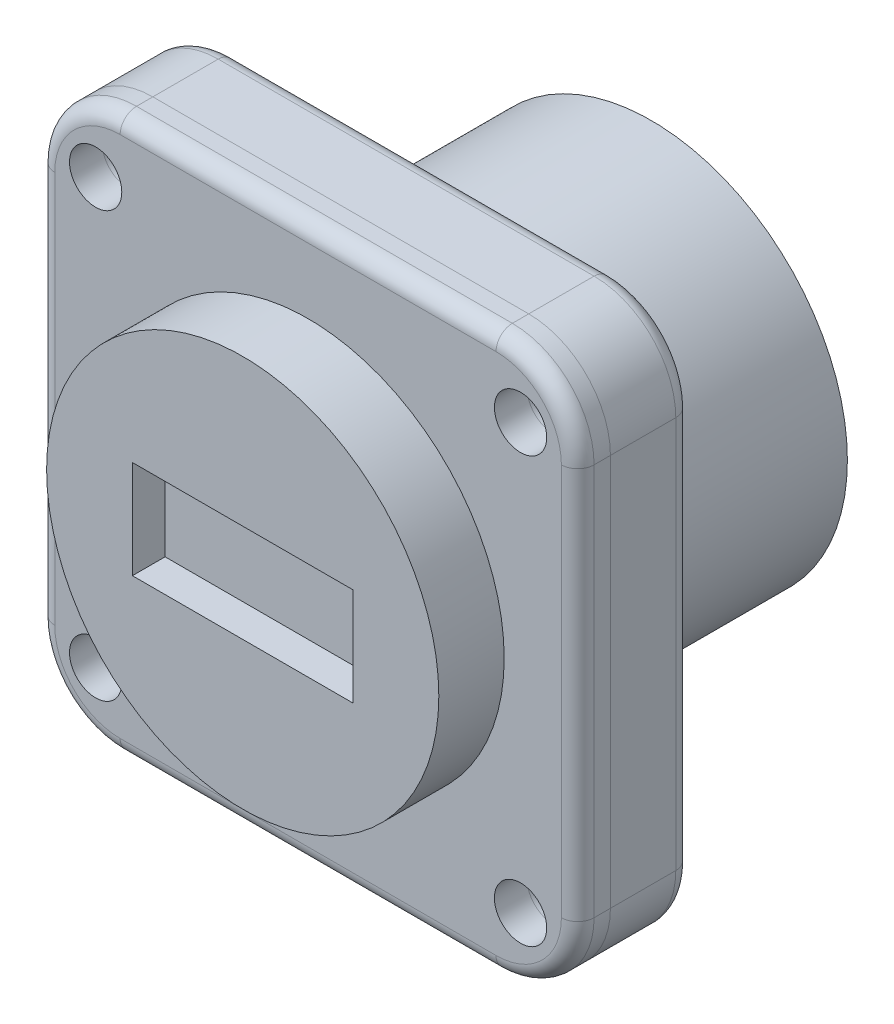
SolidWorks part; units mm, degrees
ref_plane "Front Plane" through (0, 0, 0) normal (0, 0, 1) x (1, 0, 0)
ref_plane "Top Plane" through (0, 0, 0) normal (0, 1, 0) x (1, 0, 0)
ref_plane "Right Plane" through (0, 0, 0) normal (1, 0, 0) x (0, 0, -1)
sketch "Sketch1" plane through (0, 0, 0) normal (0, 0, 1) x (1, 0, 0)
  line L0 (0, 30.4223) -> (0, -24.604) construction
  line L1 (-16.5, 17) -> (16.5, 17)
  line L2 (-16.5, 17) -> (-16.5, -17)
  line L3 (-16.5, -17) -> (16.5, -17)
  line L4 (16.5, 17) -> (16.5, -17)
  line L5 (-25.5383, 0) -> (45.6309, 0) construction
  circle A0 centre (0, 0) radius 12
  circle A1 centre (-13, 13) radius 1.6
  circle A2 centre (13, -13) radius 1.6
  circle A3 centre (13, 13) radius 1.6
  circle A4 centre (-13, -13) radius 1.6
  point P0 (0, 0)
  dimension "D3" = 24
  dimension "D4" = 3.2
  dimension "D5" = 3.2
  dimension "D1" = 34
  dimension "D2" = 33
  dimension "D6" = 13
  dimension "D7" = 13
  dimension "D8" = 13
  dimension "D9" = 13
extrude "Boss-Extrude1" add sketch "Sketch1" along normal blind 5
fillet "Fillet1" radius 5 4 edges at (-16.5, 17, 2.5) (-16.5, -17, 2.5) (16.5, -17, 2.5) (16.5, 17, 2.5)
sketch "Sketch2" plane through (0, 0, 0) normal (0, 0, -1) x (-1, 0, 0)
  circle A0 centre (0, 0) radius 12 construction
  circle A1 centre (0, 0) radius 12
extrude "Boss-Extrude2" add sketch "Sketch2" along normal blind 14 and the other way blind 5
sketch "Sketch3" plane through (0, 0, 5) normal (0, 0, 1) x (1, 0, 0)
  line L0 (-11.5, -17) -> (11.5, -17) construction
  line L1 (16.5, -12) -> (16.5, 12) construction
  line L2 (11.5, 17) -> (-11.5, 17) construction
  line L3 (-16.5, 12) -> (-16.5, -12) construction
  line L4 (-11.5, -17) -> (11.5, -17)
  line L5 (16.5, -12) -> (16.5, 12)
  line L6 (11.5, 17) -> (-11.5, 17)
  line L7 (-16.5, 12) -> (-16.5, -12)
  circle A0 centre (-13, 13) radius 1.6 construction
  circle A1 centre (13, 13) radius 1.6 construction
  circle A2 centre (13, -13) radius 1.6 construction
  circle A3 centre (-13, -13) radius 1.6 construction
  arc A4 (-16.5, -12) -> (-11.5, -17) centre (-11.5, -12) ccw construction
  arc A5 (11.5, -17) -> (16.5, -12) centre (11.5, -12) ccw construction
  arc A6 (16.5, 12) -> (11.5, 17) centre (11.5, 12) ccw construction
  arc A7 (-11.5, 17) -> (-16.5, 12) centre (-11.5, 12) ccw construction
  circle A8 centre (-13, 13) radius 1.6
  circle A9 centre (13, 13) radius 1.6
  circle A10 centre (13, -13) radius 1.6
  circle A11 centre (-13, -13) radius 1.6
  arc A12 (-16.5, -12) -> (-11.5, -17) centre (-11.5, -12) ccw
  arc A13 (11.5, -17) -> (16.5, -12) centre (11.5, -12) ccw
  arc A14 (16.5, 12) -> (11.5, 17) centre (11.5, 12) ccw
  arc A15 (-11.5, 17) -> (-16.5, 12) centre (-11.5, 12) ccw
extrude "Boss-Extrude3" add sketch "Sketch3" along normal blind 2 separate body
fillet "Fillet2" radius 1 8 edges at (15.0355, 15.5355, 0) (16.5, 0, 0) (15.0355, -15.5355, 0) (0, -17, 0) (-15.0355, -15.5355, 0) (-16.5, 0, 0) (-15.0355, 15.5355, 0) (0, 17, 0)
fillet "Fillet3" radius 1 8 edges at (15.0355, 15.5355, 7) (16.5, 0, 7) (15.0355, -15.5355, 7) (0, -17, 7) (-15.0355, -15.5355, 7) (-16.5, 0, 7) (-15.0355, 15.5355, 7) (0, 17, 7)
chamfer "Chamfer1" distance 1 angle 45 4 edges at (14.6, -13, 0) (-14.6, -13, 0) (-11.4, 13, 0) (11.4, 13, 0)
sketch "Sketch4" plane through (0, 0, 7) normal (0, 0, 1) x (1, 0, 0)
  circle A0 centre (0, 0) radius 12
  dimension "D1" = 24
extrude "Boss-Extrude4" add sketch "Sketch4" along normal blind 4
sketch "Sketch5" plane through (0, 0, -14) normal (0, 0, -1) x (-1, 0, 0)
  circle A0 centre (0, 0) radius 11.0719
extrude "Cut-Extrude1" cut sketch "Sketch5" against normal blind 4
sketch "Sketch6" plane through (0, 0, 11) normal (0, 0, 1) x (1, 0, 0)
  line L1 (-6.75, 3) -> (6.75, 3)
  line L2 (-6.75, 3) -> (-6.75, -3)
  line L3 (-6.75, -3) -> (6.75, -3)
  line L4 (6.75, 3) -> (6.75, -3)
  line L5 (-6.75, 3) -> (6.75, -3) construction
  line L6 (-6.75, -3) -> (6.75, 3) construction
  point P0 (0, 0)
  dimension "D1" = 13.5
  dimension "D2" = 6
extrude "Cut-Extrude2" cut sketch "Sketch6" against normal blind 2
sketch "Sketch7" plane through (0, 0, -10) normal (0, 0, -1) x (-1, 0, 0)
  line L0 (6.75, -3) -> (-6.75, -3) construction
  line L1 (6.75, 3) -> (6.75, -3) construction
  line L2 (-6.75, -3) -> (-6.75, 3) construction
  line L3 (-6.75, 3) -> (6.75, 3) construction
  line L4 (6.75, -3) -> (-6.75, -3)
  line L5 (6.75, 3) -> (6.75, -3)
  line L6 (-6.75, -3) -> (-6.75, 3)
  line L7 (-6.75, 3) -> (6.75, 3)
extrude "Cut-Extrude3" cut sketch "Sketch7" against normal blind 10
